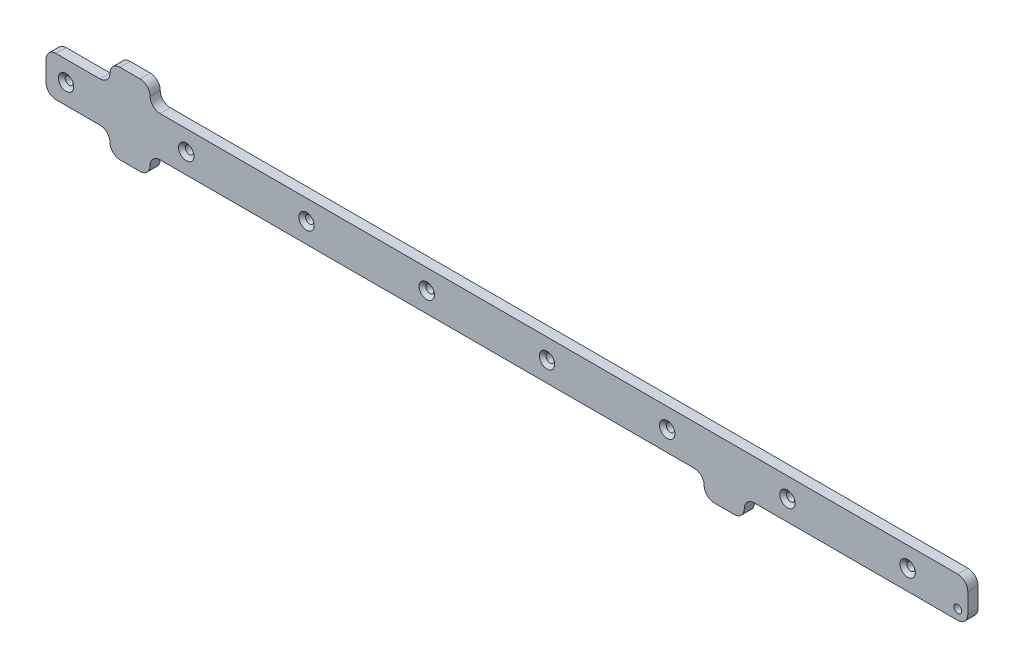
SolidWorks part; units mm, degrees
material "PC High Viscosity"
ref_plane "Front Plane" through (0, 0, 0) normal (0, 0, 1) x (1, 0, 0)
ref_plane "Top Plane" through (0, 0, 0) normal (0, 1, 0) x (1, 0, 0)
ref_plane "Right Plane" through (0, 0, 0) normal (1, 0, 0) x (0, 0, -1)
sketch "Sketch1" plane through (0, 0, 0) normal (0, 0, 1) x (1, 0, 0)
  line L0 (40.5308, 0) -> (40.5308, -12.7)
  line L1 (0, 0) -> (40.5308, 0)
  line L2 (0, 0) -> (0, 25.4)
  line L3 (0, 25.4) -> (40.5308, 25.4)
  line L4 (584.2, 0) -> (584.2, 25.4)
  line L5 (40.5308, 38.1) -> (65.9308, 38.1)
  line L6 (65.9308, 38.1) -> (65.9308, 25.4)
  line L7 (40.5308, 38.1) -> (40.5308, 25.4)
  line L8 (65.9308, 0) -> (65.9308, -12.7)
  line L9 (65.9308, -12.7) -> (40.5308, -12.7)
  line L11 (584.2, 10.0162) -> (577.85, 13.6823) construction
  line L12 (577.85, 13.6823) -> (571.5, 10.0162) construction
  line L13 (571.5, 10.0162) -> (571.5, 2.6838) construction
  line L14 (571.5, 2.6838) -> (577.85, -0.9823) construction
  line L15 (577.85, -0.9823) -> (584.2, 2.6838) construction
  line L16 (584.2, 2.6838) -> (584.2, 10.0162) construction
  line L19 (65.9308, 25.4) -> (584.2, 25.4)
  line L20 (65.9308, 0) -> (417.1409, 0)
  line L21 (442.5409, 0) -> (442.5409, -12.7)
  line L22 (442.5409, -12.7) -> (417.1409, -12.7)
  line L23 (417.1409, -12.7) -> (417.1409, 0)
  line L24 (442.5409, 0) -> (584.2, 0)
  circle A0 centre (577.85, 6.35) radius 2.4892
  circle A1 centre (577.85, 6.35) radius 6.35 construction
  point P23 (583.5224, 0)
  dimension "D5" = 4.9784
  dimension "D6" = 12.7
  dimension "D7" = 12.7
  dimension "D1" = 584.2
  dimension "D2" = 25.4
  dimension "D3" = 25.4
  dimension "D4" = 40.5308
  dimension "D10" = 167.0591
extrude "Boss-Extrude1" add sketch "Sketch1" along normal blind 6.477 contours L6 L5 L3 | L1 L4 L3 L2 A0 | L9 L8 L1 region at (284.8004, 12.3186, 0)
fillet "Fillet2" radius 6.35 16 edges at (65.9308, 38.1, 3.2385) (65.9308, -12.7, 3.2385) (40.5308, -12.7, 3.2385) (40.5308, 0, 3.2385) (0, 0, 3.2385) (40.5308, 38.1, 3.2385) (40.5308, 25.4, 3.2385) (0, 25.4, 3.2385) (65.9308, 0, 3.2385) (65.9308, 25.4, 3.2385) (442.5409, -12.7, 3.2385) (442.5409, 0, 3.2385) (417.1409, -12.7, 3.2385) (417.1409, 0, 3.2385) (584.2, 0, 3.2385) (584.2, 25.4, 3.2385)
sketch "Sketch2" plane through (0, 0, 6.477) normal (0, 0, 1) x (1, 0, 0)
  line L0 (6.35, 25.4) -> (34.1808, 25.4) construction
  line L1 (584.2, 19.05) -> (584.2, 6.35) construction
  circle A0 centre (546.1, 12.7) radius 2.0193
  dimension "D1" = 4.0386
  dimension "D2" = 12.7
  dimension "D3" = 38.1
hole_wizard "CSK for #10 Flat Head Machine Screw (100)1" positions "Sketch4" profile "Sketch5" countersink size "#10" standard "ANSI Inch" end condition through all
sketch "Sketch4" plane through (0, 0, 6.477) normal (0, 0, 1) x (1, 0, 0)
  line L0 (584.2, 12.7) -> (0, 12.7) construction
  line L1 (584.2, 19.05) -> (584.2, 6.35) construction
  line L2 (0, 6.35) -> (0, 19.05) construction
  line L3 (6.35, 25.4) -> (34.1808, 25.4) construction
  point P11 (546.1, 12.7)
  dimension "D1" = 12.7
  dimension "D2" = 38.1
sketch "Sketch5" plane through (546.1, 12.7, 6.477) normal (1, 0, 0) x (0, -1, 0)
  line L0 (0, 0) -> (0, 6.477)
  line L1 (0, 6.477) -> (2.5527, 6.477)
  line L2 (2.5527, 6.477) -> (2.5527, 1.9608)
  line L3 (2.5527, 1.9608) -> (4.8895, 0)
  line L5 (4.8895, 0) -> (0, 0)
  line L6 (-2.5527, 1.9608) -> (-4.8895, 0) construction
  line L11 (0, -6.35) -> (0, 107.95) construction
  dimension "Thru Hole Dia." = 5.1054
  dimension "Thru Hole Depth" = 6.477
  dimension "Near C'Sink Dia." = 9.779
  dimension "Near C'Sink Angle" = 100
pattern_linear "LPattern1" count 8 spacing 76.2 along (-1, 0, 0) of "CSK for #10 Flat Head Machine Screw (100)1"
